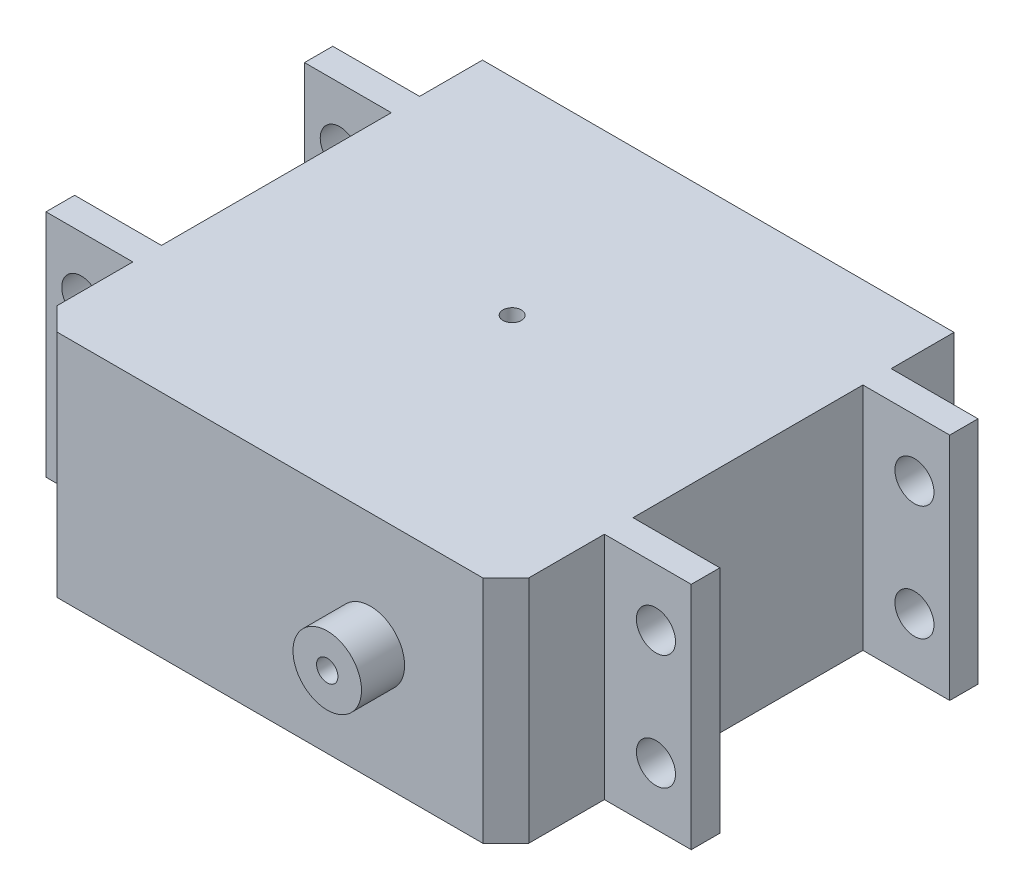
SolidWorks part; units mm, degrees
ref_plane "Front Plane" through (0, 0, 0) normal (0, 0, 1) x (1, 0, 0)
ref_plane "Top Plane" through (0, 0, 0) normal (0, 1, 0) x (1, 0, 0)
ref_plane "Right Plane" through (0, 0, 0) normal (1, 0, 0) x (0, 0, -1)
sketch "Sketch1" plane through (0, 0, 0) normal (0, 0, 1) x (1, 0, 0)
  line L1 (28.07, -10) -> (-28.07, -10)
  line L2 (28.07, -10) -> (28.07, 10)
  line L3 (28.07, 10) -> (-28.07, 10)
  line L4 (-28.07, -10) -> (-28.07, 10)
  line L5 (28.07, -10) -> (-28.07, 10) construction
  line L6 (28.07, 10) -> (-28.07, -10) construction
  point P0 (0, 0)
  dimension "D1" = 56.14
  dimension "D2" = 20
extrude "Boss-Extrude1" add sketch "Sketch1" along normal blind 2.49
hole_wizard "M3 Clearance Hole1" positions "Sketch3" profile "Sketch2" hole size "M3" standard "DIN"
sketch "Sketch3" plane through (0, 0, 2.49) normal (0, 0, 1) x (1, 0, 0)
  line L1 (25, -5) -> (-25, -5)
  line L2 (25, -5) -> (25, 5)
  line L3 (25, 5) -> (-25, 5)
  line L4 (-25, -5) -> (-25, 5)
  line L5 (25, -5) -> (-25, 5) construction
  line L6 (25, 5) -> (-25, -5) construction
  point P0 (25, 5)
  point P2 (0, 0)
  point P70 (-25, 5)
  point P72 (-25, -5)
  point P74 (25, -5)
  dimension "D1" = 50
  dimension "D2" = 10
sketch "Sketch2" plane through (25, 5, 2.49) normal (1, 0, 0) x (0, -1, 0)
  line L0 (0, 0) -> (0, 20.0215)
  line L1 (0, 20.0215) -> (1.7, 19)
  line L2 (1.7, 19) -> (1.7, 0)
  line L5 (1.7, 0) -> (0, 0)
  line L10 (0, 20.0215) -> (-1.7, 19) construction
  line L11 (0, -6.35) -> (0, 107.95) construction
  dimension "Hole Dia." = 3.4
  dimension "Hole Depth" = 19
  dimension "Drill Angle" = 118
sketch "Sketch4" plane through (0, 0, 2.49) normal (0, 0, 1) x (1, 0, 0)
  line L1 (20.515, -10) -> (-20.515, -10)
  line L2 (20.515, -10) -> (20.515, 10)
  line L3 (20.515, 10) -> (-20.515, 10)
  line L4 (-20.515, -10) -> (-20.515, 10)
  line L5 (20.515, -10) -> (-20.515, 10) construction
  line L6 (20.515, 10) -> (-20.515, -10) construction
  point P0 (0, 0)
  dimension "D1" = 41.03
  dimension "D2" = 20
extrude "Boss-Extrude2" add sketch "Sketch4" along normal blind 8.58
sketch "Sketch5" plane through (0, 0, 11.07) normal (0, 0, 1) x (1, 0, 0)
  circle A0 centre (8.73, 0) radius 2.98
  circle A1 centre (8.73, 0) radius 0.929
  dimension "D1" = 5.96
  dimension "D2" = 8.73
extrude "Boss-Extrude3" add sketch "Sketch5" along normal blind 3.75
sketch "Sketch6" plane through (0, 0, 0) normal (0, 0, -1) x (-1, 0, 0)
  line L0 (0, 0) -> (0, -13.4805) construction
  line L1 (-20.75, 10) -> (-28.75, 10)
  line L2 (-20.75, 10) -> (-20.75, -10)
  line L3 (-20.75, -10) -> (-28.75, -10)
  line L4 (-28.75, 10) -> (-28.75, -10)
  line L5 (-20.75, 10) -> (-28.75, -10) construction
  line L6 (-20.75, -10) -> (-28.75, 10) construction
  line L7 (-28.07, 10) -> (28.07, 10) construction
  line L8 (20.75, -10) -> (28.75, 10) construction
  line L9 (20.75, 10) -> (28.75, -10) construction
  line L10 (28.75, 10) -> (28.75, -10)
  line L11 (20.75, -10) -> (28.75, -10)
  line L12 (20.75, 10) -> (20.75, -10)
  line L13 (20.75, 10) -> (28.75, 10)
  point P0 (-24.75, 0)
  point P14 (24.75, 0)
  dimension "D1" = 8
  dimension "D2" = 57.5
extrude "Boss-Extrude4" add sketch "Sketch6" along normal blind 20 separate body
sketch "Sketch7" plane through (0, 0, 0) normal (0, 0, -1) x (-1, 0, 0)
  line L1 (20.515, -10) -> (-20.515, -10)
  line L2 (20.515, -10) -> (20.515, 10)
  line L3 (20.515, 10) -> (-20.515, 10)
  line L4 (-20.515, -10) -> (-20.515, 10)
  line L5 (20.515, -10) -> (-20.515, 10) construction
  line L6 (20.515, 10) -> (-20.515, -10) construction
  point P0 (0, 0)
extrude "Boss-Extrude5" add sketch "Sketch7" along normal up to surface (20 mm away) up to face at (24.75, 0, -20)
sketch "Sketch8" plane through (0, 0, -20) normal (0, 0, -1) x (-1, 0, 0)
  line L0 (-20.75, 10) -> (-28.75, 10) construction
  line L1 (28.07, -10) -> (-28.07, -10)
  line L2 (28.07, -10) -> (28.07, 10)
  line L3 (28.07, 10) -> (-28.07, 10)
  line L4 (-28.07, -10) -> (-28.07, 10)
  line L5 (28.07, -10) -> (-28.07, 10) construction
  line L6 (28.07, 10) -> (-28.07, -10) construction
  line L7 (-28.07, -10) -> (-28.07, 10) construction
  point P0 (0, 0)
extrude "Boss-Extrude6" add sketch "Sketch8" along normal offset from surface (2.46 mm away) 24.95 up to face at (24.2925, -2.5, 2.49)
hole_wizard "M3 Clearance Hole2" positions "Sketch11" profile "Sketch12" hole size "M3" standard "DIN" end condition through all
sketch "Sketch11" plane through (0, 0, 2.49) normal (0, 0, 1) x (1, 0, 0)
  point P0 (25, 5)
  point P1 (25, -5)
  point P3 (-25, 5)
  point P5 (-25, -5)
sketch "Sketch12" plane through (25, 5, 2.49) normal (1, 0, 0) x (0, -1, 0)
  line L0 (0, 0) -> (0, 24.95)
  line L1 (0, 24.95) -> (1.7, 24.95)
  line L2 (1.7, 24.95) -> (1.7, 0)
  line L5 (1.7, 0) -> (0, 0)
  line L11 (0, -6.35) -> (0, 107.95) construction
  dimension "Thru Hole Dia." = 3.4
  dimension "Thru Hole Depth" = 24.95
sketch "Sketch13" plane through (0, 0, 11.07) normal (0, 0, 1) x (1, 0, 0)
  line L1 (20.515, -10) -> (-20.515, -10)
  line L2 (20.515, -10) -> (20.515, 10)
  line L3 (20.515, 10) -> (-20.515, 10)
  line L4 (-20.515, -10) -> (-20.515, 10)
  line L5 (20.515, -10) -> (-20.515, 10) construction
  line L6 (20.515, 10) -> (-20.515, -10) construction
  point P0 (0, 0)
extrude "Boss-Extrude7" add sketch "Sketch13" against normal blind 39
sketch "Sketch14" plane through (0, 0, -27.93) normal (0, 0, -1) x (-1, 0, 0)
  circle A0 centre (-8.73, 0) radius 4
  circle A1 centre (-8.73, 0) radius 1.25
  dimension "D1" = 8
  dimension "D2" = 2.5
extrude "Boss-Extrude8" add sketch "Sketch14" along normal offset from surface (5.37 mm away) 48.12 up to face at (11.71, 0, 14.82)
hole_wizard "Tap Drill for M2 Tap1" positions "Sketch17" profile "Sketch16" hole size "M2" standard "DIN" end condition through all
sketch "Sketch17" plane through (0, -10, 0) normal (0, -1, 0) x (1, 0, 0)
  line L1 (25, -15) -> (-25, -15)
  line L2 (25, -15) -> (25, -5)
  line L3 (25, -5) -> (-25, -5)
  line L4 (-25, -15) -> (-25, -5)
  line L5 (25, -15) -> (-25, -5) construction
  line L6 (25, -5) -> (-25, -15) construction
  line L7 (-28.75, 0) -> (28.75, -20) construction
  point P0 (-25, -5)
  point P2 (0, -10)
  point P123 (-25, -15)
  point P127 (25, -5)
  point P129 (25, -15)
  dimension "D1" = 50
  dimension "D2" = 10
sketch "Sketch16" plane through (-25, -10, -5) normal (1, 0, 0) x (0, 0, -1)
  line L0 (0, 0) -> (0, 20.0001)
  line L1 (0, 20.0001) -> (0.8, 20.0001)
  line L2 (0.8, 20.0001) -> (0.8, 0)
  line L5 (0.8, 0) -> (0, 0)
  line L11 (0, -6.35) -> (0, 107.95) construction
  dimension "Thru Hole Dia." = 1.6
  dimension "Thru Hole Depth" = 20.0001
chamfer "Chamfer1" distance 2 angle 45 2 edges at (-20.515, 0, 11.07) (20.515, 0, 11.07)
sketch "Sketch19" plane through (0, 0, -27.93) normal (0, 0, -1) x (-1, 0, 0)
  circle A0 centre (-8.73, 0) radius 6.18
  circle A1 centre (-8.73, 0) radius 4
  circle A2 centre (-8.73, 0) radius 4 construction
  dimension "D1" = 12.36
extrude "Boss-Extrude10" add sketch "Sketch19" along normal blind 2.12
sketch "Sketch20" plane through (0, 0, -16.54) normal (0, 0, 1) x (1, 0, 0)
  line L0 (20.515, 10) -> (20.515, -10) construction
  line L1 (33.6922, 20.7249) -> (20.515, 20.7249)
  line L2 (33.6922, 20.7249) -> (33.6922, 19.7249)
  line L3 (33.6922, 19.7249) -> (20.515, 19.7249)
  line L4 (20.515, 20.7249) -> (20.515, 19.7249)
  line L6 (0, 9.7249) -> (34.4309, 9.7249) construction
  dimension "D1" = 20
  dimension "D2" = 1
sketch "Sketch21" plane through (0, 10, 0) normal (0, 1, 0) x (1, 0, 0)
  line L0 (-28.75, 20) -> (-28.75, 0) construction
  line L1 (-28.75, 13.5) -> (-20.75, 13.5)
  line L2 (-28.75, 13.5) -> (-28.75, 6.5)
  line L3 (-28.75, 6.5) -> (-20.75, 6.5)
  line L4 (-20.75, 13.5) -> (-20.75, 6.5)
  line L5 (-20.75, 20) -> (-20.75, 0) construction
  line L6 (28.75, 20) -> (28.75, 0) construction
  line L7 (28.75, 6.5) -> (20.75, 6.5)
  line L8 (28.75, 6.5) -> (28.75, 13.5)
  line L9 (28.75, 13.5) -> (20.75, 13.5)
  line L10 (20.75, 6.5) -> (20.75, 13.5)
  line L11 (20.75, 20) -> (20.75, 0) construction
  line L12 (-28.75, 10) -> (-34.9293, 10) construction
  dimension "D1" = 7
extrude "Cut-Extrude1" cut sketch "Sketch21" against normal blind 28
sketch "Sketch22" plane through (-28.75, 0, 0) normal (-1, 0, 0) x (0, 0, 1)
  line L1 (-20, -10) -> (0, -10)
  line L2 (-20, -10) -> (-20, 10)
  line L3 (-20, 10) -> (0, 10)
  line L4 (0, -10) -> (0, 10)
extrude "Cut-Extrude2" cut sketch "Sketch22" against normal up to surface (8.235 mm away) up to face at (-20.515, 0, -15)
sketch "Sketch23" plane through (28.75, 0, 0) normal (1, 0, 0) x (0, 0, -1)
  line L1 (20, 10) -> (0, 10)
  line L2 (20, 10) -> (20, -10)
  line L3 (20, -10) -> (0, -10)
  line L4 (0, 10) -> (0, -10)
extrude "Cut-Extrude3" cut sketch "Sketch23" against normal up to surface (8.235 mm away) up to face at (20.515, 0, -15)
